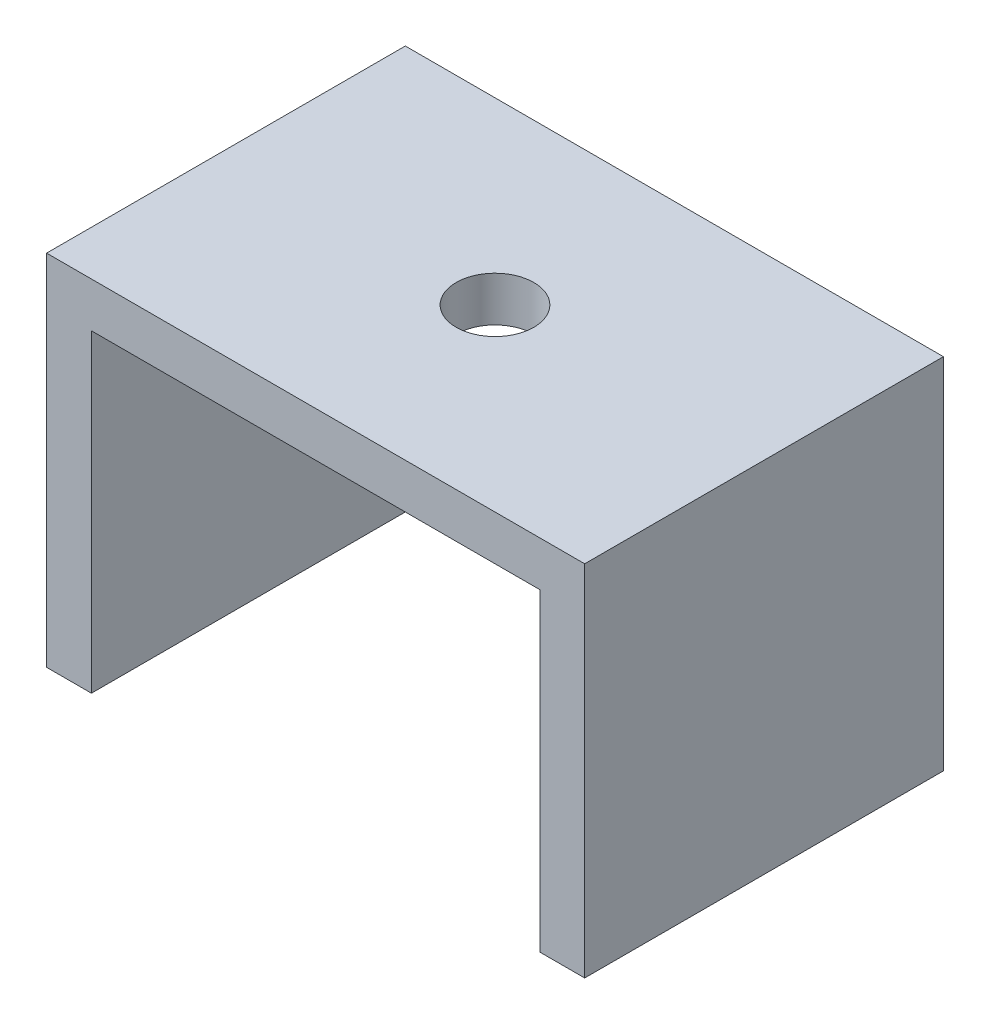
SolidWorks part; units mm, degrees
material "6063-O"
ref_plane "Front" through (0, 0, 0) normal (0, 0, 1) x (1, 0, 0)
ref_plane "Top" through (0, 0, 0) normal (0, 1, 0) x (1, 0, 0)
ref_plane "Right" through (0, 0, 0) normal (1, 0, 0) x (0, 0, -1)
sketch "Sketch1" plane through (0, 0, 0) normal (0, 0, 1) x (1, 0, 0)
  line L0 (0, 0) -> (0, 48916.6043) construction
  line L1 (38.1, 6.35) -> (-38.1, 6.35)
  line L2 (-38.1, 6.35) -> (-38.1, -44.45)
  line L3 (-38.1, -44.45) -> (-31.75, -44.45)
  line L4 (-31.75, -44.45) -> (-31.75, 0)
  line L5 (-31.75, 0) -> (31.75, 0)
  line L6 (38.1, -44.45) -> (31.75, -44.45)
  line L7 (31.75, -44.45) -> (31.75, 0)
  line L8 (38.1, 6.35) -> (38.1, -44.45)
  point P5 (-31.75, -41.499)
  point P10 (0, 0)
  point P12 (0, 0)
  point P15 (0, 6.35)
  dimension "D1" = 38.1
  dimension "D2" = 31.75
  dimension "D3" = 50.8
  dimension "D4" = 6.35
extrude "Boss-Extrude1" add sketch "Sketch1" along normal blind 50.8
sketch "Sketch2" plane through (0, 6.35, 0) normal (0, 1, 0) x (1, 0, 0)
  line L0 (0, 0) -> (0, -50.8) construction
  line L1 (38.1, -50.8) -> (-38.1, -50.8) construction
  circle A0 centre (0, -25.4) radius 5.5
  dimension "D1" = 11
extrude "Cut-Extrude1" cut sketch "Sketch2" against normal blind 50.8
